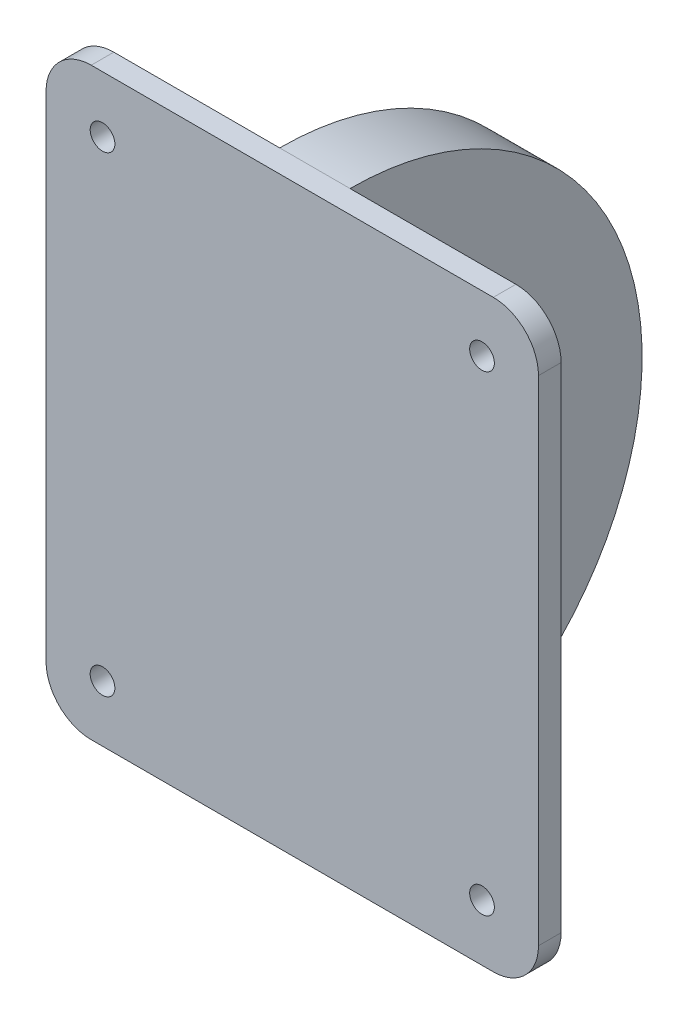
SolidWorks part; units mm, degrees
material "PE High Density"
ref_plane "Front Plane" through (0, 0, 0) normal (0, 0, 1) x (1, 0, 0)
ref_plane "Top Plane" through (0, 0, 0) normal (0, 1, 0) x (1, 0, 0)
ref_plane "Right Plane" through (0, 0, 0) normal (1, 0, 0) x (0, 0, -1)
sketch "Sketch1" plane through (0, 0, 0) normal (0, 0, 1) x (1, 0, 0)
  line L1 (-21.799, 25.8583) -> (21.799, 25.8583)
  line L2 (-21.799, 25.8583) -> (-21.799, -25.8583)
  line L3 (-21.799, -25.8583) -> (21.799, -25.8583)
  line L4 (21.799, 25.8583) -> (21.799, -25.8583)
  line L5 (-21.799, 25.8583) -> (21.799, -25.8583) construction
  line L6 (-21.799, -25.8583) -> (21.799, 25.8583) construction
  point P0 (0, 0)
  dimension "D1" = 51.7166
  dimension "D2" = 43.598
extrude "Boss-Extrude1" add sketch "Sketch1" along normal blind 2
fillet "Fillet1" radius 4 4 edges at (-21.799, -25.8583, 1) (21.799, -25.8583, 1) (-21.799, 25.8583, 1) (21.799, 25.8583, 1)
sketch "Sketch2" plane through (0, 0, 2) normal (0, 0, 1) x (1, 0, 0)
  line L0 (17.799, 25.8583) -> (-17.799, 25.8583) construction
  line L1 (-21.799, 21.8583) -> (-21.799, -21.8583) construction
  line L2 (21.799, -21.8583) -> (21.799, 21.8583) construction
  line L3 (-17.799, -25.8583) -> (17.799, -25.8583) construction
  circle A0 centre (-16.799, 20.8583) radius 1.0922
  circle A1 centre (16.799, 20.8583) radius 1.0922
  circle A2 centre (-16.799, -20.8583) radius 1.0922
  circle A3 centre (16.799, -20.8583) radius 1.0922
  dimension "D1" = 2.1844
  dimension "D2" = 2.1844
  dimension "D3" = 2.1844
  dimension "D4" = 2.1844
  dimension "D5" = 5
  dimension "D6" = 5
  dimension "D7" = 5
  dimension "D8" = 5
  dimension "D9" = 5
  dimension "D10" = 5
  dimension "D11" = 5
  dimension "D12" = 5
extrude "Cut-Extrude1" cut sketch "Sketch2" against normal blind 2
cosmetic thread "Cosmetic Thread1" parameters "D2"=3.1844
cosmetic thread "Cosmetic Thread2" parameters "D2"=3.1844
cosmetic thread "Cosmetic Thread3" parameters "D2"=3.1844
cosmetic thread "Cosmetic Thread4" parameters "D2"=3.1844
sketch "Sketch5" plane through (0, 0, 0) normal (1, 0, 0) x (0, 0, -1)
  line L0 (0, 25.8583) -> (0, -25.8583) construction
  line L1 (0, 25.8583) -> (0, -25.8583)
  arc A0 (0, -25.8583) -> (0, 25.8583) centre (0, 0) ccw
  dimension "D1" = 51.7166
extrude "Boss-Extrude2" add sketch "Sketch5" along normal mid plane 6.2325
sketch "Sketch6" plane through (3.1162, 0, 0) normal (1, 0, 0) x (0, 0, -1)
  line L0 (0, -21.8583) -> (0, 21.8583) construction
  line L1 (0, -25.8583) -> (-2, -25.8583) construction
  circle A0 centre (10.61, 0) radius 5
  dimension "D2" = 10
  dimension "D1" = 10.61
  dimension "D3" = 25.8583
extrude "Cut-Extrude2" cut sketch "Sketch6" against normal up to next
equation "\"userHeight\"= 1750mm'Users height"
equation "\"fin_hole_radius\"= 10mm'Fin hole radius"
equation "\"fin_thickness\"=6.23245771"
equation "\"D1\"= \"fin_thickness\""
equation "\"D2@Sketch6\"=\"fin_hole_radius\""
equation "\"D1@Boss-Extrude2\"=\"fin_thickness\""
equation "\"fin_platform_width\"= 43.598"
equation "\"D2@Sketch1\"=\"fin_platform_width\""
equation "\"fin_platform_height\"= 51.7166"
equation "\"D1@Sketch1\"=\"fin_platform_height\""
equation "\"hole_position_y\"= 25 * \"fin_platform_height\" / 50'Fin platform position y"
equation "\"D3@Sketch6\"=\"hole_position_y\""
equation "\"D1@Sketch5\"=\"fin_platform_height\""
equation "\"shell_outer_radius\"= 86.723"
equation "\"partial_sidebar_length\"=284.34850000"
equation "\"shell_length\"=145.01147666"
